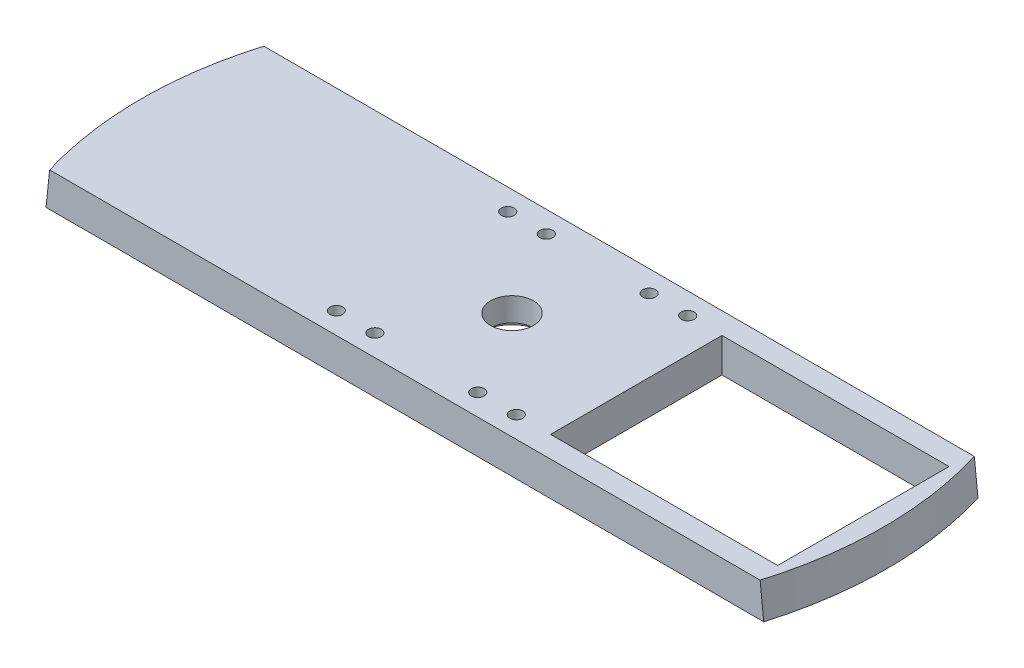
SolidWorks part; units mm, degrees
material "Acrylic (Medium-high impact)"
ref_plane "Front Plane" through (0, 0, 0) normal (0, 0, 1) x (1, 0, 0)
ref_plane "Top Plane" through (0, 0, 0) normal (0, 1, 0) x (1, 0, 0)
ref_plane "Right Plane" through (0, 0, 0) normal (1, 0, 0) x (0, 0, -1)
sketch "Chassi Outline Sketch" plane through (0, 0, 0) normal (0, 0, 1) x (1, 0, 0)
  line L0 (0, 0) -> (0, 128) construction
  line L1 (0, 0) -> (109.2209, 0) construction
  line L2 (91.6709, 0) -> (85.17, 64) construction
  line L3 (85.17, 64) -> (-85.17, 64) construction
  line L4 (85.17, 75.9083) -> (85.17, 0) construction
  line L5 (-91.6709, 0) -> (-85.17, 64) construction
  line L6 (0, 0) -> (-164.8351, 0) construction
  point P11 (0, 64)
  dimension "D1" = 5.8
  dimension "D2" = 85.17
  dimension "D3" = 64
  dimension "D4" = 183.3418
  dimension "D5" = 170.34
sketch "Chassi Outline Round Sketch" plane through (0, 0, 0) normal (0, 1, 0) x (1, 0, 0)
  circle A0 centre (0, 0) radius 85.17 construction
sketch "Sketch2" plane through (0, 0, 0) normal (0, 0, 1) x (1, 0, 0)
  line L0 (0, 0) -> (0, 128) construction
  line L1 (-86.5921, 50) -> (86.5921, 50)
  line L2 (87.4047, 42) -> (86.5921, 50)
  line L3 (-87.4047, 42) -> (87.4047, 42)
  line L4 (85.17, 64) -> (-85.17, 64) construction
  line L5 (91.6709, 0) -> (85.17, 64) construction
  line L6 (0, 0) -> (0, 83.0892) construction
  line L7 (-87.4047, 42) -> (-86.5921, 50)
  point P2 (0, 50)
  point P15 (0, 42)
  dimension "D1" = 8
  dimension "D2" = 14
extrude "Top Plate Boss-Extrude1" add sketch "Sketch2" along normal blind 25 and the other way blind 25
sketch "Sketch4" plane through (0, 0, 0) normal (0, 0, 1) x (1, 0, 0)
  line L0 (86.5921, 50) -> (87.4047, 42)
  line L1 (87.4047, 42) -> (97.785, 42)
  line L2 (97.785, 42) -> (97.785, 50)
  line L3 (97.785, 50) -> (86.5921, 50)
  line L4 (91.6709, 0) -> (85.17, 64) construction
  line L5 (86.5921, 50) -> (-86.5921, 50) construction
  line L6 (-87.4047, 42) -> (87.4047, 42) construction
revolve "Top Plate Chassi Rounding Cut-Revolve1" cut sketch "Sketch4" angle 360 about L0
sketch "Sketch5" plane through (0, 42, 0) normal (0, -1, 0) x (1, 0, 0)
  circle A0 centre (0, 0) radius 5
  dimension "D1" = 10
extrude "Shaft Cut-Extrude1" cut sketch "Sketch5" against normal up to surface (8 mm away) up to face at (0, 50, 0)
sketch "Sketch6" plane through (0, 42, 0) normal (0, -1, 0) x (1, 0, 0)
  circle A0 centre (0, 0) radius 8
  dimension "D1" = 16
extrude "Shaft Bearing Cut-Extrude2" cut sketch "Sketch6" against normal blind 2.5
sketch "Sketch7" plane through (0, 42, 0) normal (0, -1, 0) x (1, 0, 0)
  line L0 (0, 0) -> (25, 0) construction
  line L1 (85.17, 0) -> (-85.17, 0) construction
  line L2 (0, 0) -> (-25, 0) construction
  line L3 (25, 0) -> (25, 25) construction
  line L4 (-83.7531, 25) -> (83.7531, 25) construction
  line L5 (25, 0) -> (25, -25) construction
  line L6 (-83.7531, -25) -> (83.7531, -25) construction
  line L7 (-25, 0) -> (-25, 25) construction
  line L8 (-25, 0) -> (-25, -25) construction
  line L9 (-17, 25) -> (-17, -25) construction
  line L10 (17, 25) -> (17, -25) construction
  line L11 (12, -20) -> (0, 0) construction
  line L12 (-12, 20) -> (12, 20) construction
  line L13 (-12, 20) -> (-12, -20) construction
  line L14 (-12, -20) -> (12, -20) construction
  line L15 (12, 20) -> (12, -20) construction
  line L16 (0, 0) -> (-12, -20) construction
  line L17 (0, 0) -> (-12, 20) construction
  line L18 (0, 0) -> (12, 20) construction
  circle A0 centre (12, 20) radius 1.5
  circle A1 centre (-12, 20) radius 1.5
  circle A2 centre (-12, -20) radius 1.5
  circle A3 centre (12, -20) radius 1.5
  dimension "D4" = 3
  dimension "D1" = 50
  dimension "D2" = 8
  dimension "D3" = 8
  dimension "D5" = 5
  dimension "D6" = 5
extrude "Bearing Plate Mounting Holes Cut-Extrude3" cut sketch "Sketch7" against normal up to surface (8 mm away) up to face at (-5, 50, 0)
sketch "Sketch8" plane through (0, 42, 0) normal (0, -1, 0) x (1, 0, 0)
  line L0 (0, 0) -> (25, 0) construction
  line L1 (85.17, 0) -> (-85.17, 0) construction
  line L2 (0, 0) -> (-25, 0) construction
  line L3 (25, 25) -> (25, -25) construction
  line L4 (-83.7531, 25) -> (83.7531, 25) construction
  line L5 (-83.7531, -25) -> (83.7531, -25) construction
  line L6 (-25, 25) -> (-25, -25) construction
  line L7 (-17, 25) -> (-17, -25) construction
  line L8 (17, 25) -> (17, -25) construction
  line L9 (-21, 20) -> (0, 0) construction
  line L10 (21, 20) -> (-21, 20) construction
  line L11 (21, 20) -> (21, -20) construction
  line L12 (21, -20) -> (-21, -20) construction
  line L13 (-21, 20) -> (-21, -20) construction
  line L14 (0, 0) -> (21, 20) construction
  line L15 (0, 0) -> (21, -20) construction
  line L16 (0, 0) -> (-21, -20) construction
  circle A0 centre (21, 20) radius 1.5
  circle A1 centre (-21, 20) radius 1.5
  circle A2 centre (-21, -20) radius 1.5
  circle A3 centre (21, -20) radius 1.5
  dimension "D6" = 3
  dimension "D1" = 50
  dimension "D2" = 8
  dimension "D3" = 8
  dimension "D4" = 4
  dimension "D5" = 5
extrude "Base Side Mounting Holes Cut-Extrude4" cut sketch "Sketch8" against normal up to surface (8 mm away) up to face at (10.5, 50, -20)
sketch "Sketch9" plane through (0, 50, 0) normal (0, 1, 0) x (1, 0, 0)
  line L0 (82.9047, 25) -> (-82.9047, 25) construction
  line L1 (29, 20) -> (82, 20)
  line L2 (29, 20) -> (29, -20)
  line L3 (29, -20) -> (82, -20)
  line L4 (82, 20) -> (82, -20)
  line L5 (82.9047, -25) -> (-82.9047, -25) construction
  circle A0 centre (21, -20) radius 1.5 construction
  dimension "D5" = 8
  dimension "D1" = 5
  dimension "D2" = 5
  dimension "D3" = 40
  dimension "D4" = 53
extrude "Timing Belt Slider Hole Cut-Extrude1" cut sketch "Sketch9" against normal up to surface (8 mm away) up to face at (22.5, 42, -20)
